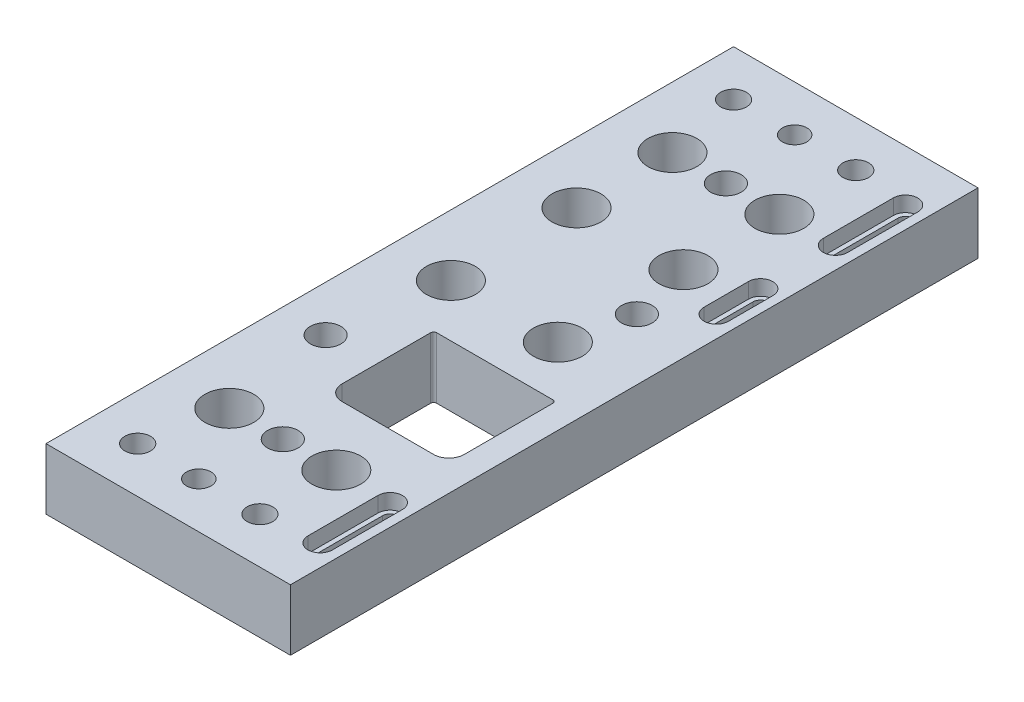
SolidWorks part; units mm, degrees
material "Plain Carbon Steel"
ref_plane "Front Plane" through (0, 0, 0) normal (0, 0, 1) x (1, 0, 0)
ref_plane "Top Plane" through (0, 0, 0) normal (0, 1, 0) x (1, 0, 0)
ref_plane "Right Plane" through (0, 0, 0) normal (1, 0, 0) x (0, 0, -1)
sketch "Sketch1" plane through (0, 0, 0) normal (0, 1, 0) x (1, 0, 0)
  line L1 (-40, -112.5) -> (40, -112.5)
  line L2 (-40, -112.5) -> (-40, 112.5)
  line L3 (-40, 112.5) -> (40, 112.5)
  line L4 (40, -112.5) -> (40, 112.5)
  line L5 (-40, -112.5) -> (40, 112.5) construction
  line L6 (-40, 112.5) -> (40, -112.5) construction
  point P0 (0, 0)
  dimension "D1" = 225
  dimension "D2" = 80
extrude "Boss-Extrude1" add sketch "Sketch1" against normal blind 20
sketch "Sketch2" plane through (0, 0, 0) normal (0, 1, 0) x (1, 0, 0)
  line L0 (23, -52.14) -> (26.5, -52.14) construction
  line L2 (31.5, -47.14) -> (31.5, -19.64) construction
  line L4 (31.5, -47.14) -> (31.5, -18.14)
  line L5 (-3.5, -52.14) -> (26.5, -52.14)
  line L6 (-8.5, -18.14) -> (-8.5, -47.14)
  line L7 (-7.5, -17.14) -> (30.5, -17.14)
  arc A2 (26.5, -52.14) -> (31.5, -47.14) centre (26.5, -47.14) ccw construction
  arc A5 (26.5, -52.14) -> (31.5, -47.14) centre (26.5, -47.14) ccw
  arc A6 (-8.5, -47.14) -> (-3.5, -52.14) centre (-3.5, -47.14) ccw
  arc A7 (30.5, -17.14) -> (31.5, -18.14) centre (30.5, -18.14) cw
  arc A8 (-7.5, -17.14) -> (-8.5, -18.14) centre (-7.5, -18.14) ccw
  dimension "D1" = 5
  dimension "D3" = 1
  dimension "D2" = 40
  dimension "D4" = 35
extrude "Cut-Extrude1" cut sketch "Sketch2" against normal up to next
sketch "Sketch3" plane through (0, 0, 0) normal (0, 1, 0) x (1, 0, 0)
  line L4 (35.5, -95.77) -> (35.5, -72.87)
  line L5 (30.5, -72.87) -> (30.5, -95.77)
  line L6 (35.5, -95.77) -> (35.5, -72.87)
  line L7 (30.5, -72.87) -> (30.5, -95.77)
  line L10 (35.5, 33.86) -> (35.5, 48.36)
  line L11 (30.5, 48.36) -> (30.5, 33.86)
  line L12 (35.5, 33.86) -> (35.5, 48.36)
  line L13 (30.5, 48.36) -> (30.5, 33.86)
  line L16 (35.5, 72.87) -> (35.5, 95.77)
  line L17 (30.5, 95.77) -> (30.5, 72.87)
  line L18 (35.5, 72.87) -> (35.5, 95.77)
  line L19 (30.5, 95.77) -> (30.5, 72.87)
  arc A4 (35.5, -72.87) -> (30.5, -72.87) centre (33, -72.87) ccw
  arc A5 (30.5, -95.77) -> (35.5, -95.77) centre (33, -95.77) ccw
  arc A6 (35.5, -72.87) -> (30.5, -72.87) centre (33, -72.87) ccw
  arc A7 (30.5, -95.77) -> (35.5, -95.77) centre (33, -95.77) ccw
  arc A10 (35.5, 48.36) -> (30.5, 48.36) centre (33, 48.36) ccw
  arc A11 (30.5, 33.86) -> (35.5, 33.86) centre (33, 33.86) ccw
  arc A12 (35.5, 48.36) -> (30.5, 48.36) centre (33, 48.36) ccw
  arc A13 (30.5, 33.86) -> (35.5, 33.86) centre (33, 33.86) ccw
  arc A16 (35.5, 95.77) -> (30.5, 95.77) centre (33, 95.77) ccw
  arc A17 (30.5, 72.87) -> (35.5, 72.87) centre (33, 72.87) ccw
  arc A18 (35.5, 95.77) -> (30.5, 95.77) centre (33, 95.77) ccw
  arc A19 (30.5, 72.87) -> (35.5, 72.87) centre (33, 72.87) ccw
  dimension "D1" = 0.05
  dimension "D2" = 0.05
  dimension "D3" = 0.05
extrude "Cut-Extrude2" cut sketch "Sketch3" against normal up to next
sketch "Sketch4" plane through (0, 0, 0) normal (0, 1, 0) x (1, 0, 0)
  line L4 (37, 72.87) -> (37, 95.77)
  line L5 (29, 95.77) -> (29, 72.87)
  line L6 (37, 72.87) -> (37, 95.77)
  line L7 (29, 95.77) -> (29, 72.87)
  line L10 (37, 33.86) -> (37, 48.36)
  line L11 (29, 48.36) -> (29, 33.86)
  line L12 (37, 33.86) -> (37, 48.36)
  line L13 (29, 48.36) -> (29, 33.86)
  line L16 (37, -95.77) -> (37, -72.87)
  line L17 (29, -72.87) -> (29, -95.77)
  line L18 (37, -95.77) -> (37, -72.87)
  line L19 (29, -72.87) -> (29, -95.77)
  arc A4 (37, 95.77) -> (29, 95.77) centre (33, 95.77) ccw
  arc A5 (29, 72.87) -> (37, 72.87) centre (33, 72.87) ccw
  arc A6 (37, 95.77) -> (29, 95.77) centre (33, 95.77) ccw
  arc A7 (29, 72.87) -> (37, 72.87) centre (33, 72.87) ccw
  arc A10 (37, 48.36) -> (29, 48.36) centre (33, 48.36) ccw
  arc A11 (29, 33.86) -> (37, 33.86) centre (33, 33.86) ccw
  arc A12 (37, 48.36) -> (29, 48.36) centre (33, 48.36) ccw
  arc A13 (29, 33.86) -> (37, 33.86) centre (33, 33.86) ccw
  arc A16 (37, -72.87) -> (29, -72.87) centre (33, -72.87) ccw
  arc A17 (29, -95.77) -> (37, -95.77) centre (33, -95.77) ccw
  arc A18 (37, -72.87) -> (29, -72.87) centre (33, -72.87) ccw
  arc A19 (29, -95.77) -> (37, -95.77) centre (33, -95.77) ccw
  dimension "D1" = 1.5
  dimension "D2" = 1.5
  dimension "D3" = 1.5
extrude "Cut-Extrude3" cut sketch "Sketch4" against normal blind 5
hole_wizard "CBORE for M8 Hex Head Bolt1" positions "Sketch9" profile "Sketch8" counterbore size "M8" standard "ISO" end condition through all
sketch "Sketch9" plane through (0, -20, 0) normal (0, -1, 0) x (-1, 0, 0)
  line L0 (40, -112.5) -> (-40, -112.5) construction
  line L1 (-40, -112.5) -> (-40, 112.5) construction
  line L2 (40, 112.5) -> (40, -112.5) construction
  line L3 (-40, 112.5) -> (40, 112.5) construction
  point P0 (25, 97.5)
  point P2 (-15, 97.5)
  point P4 (-15, -97.5)
  point P6 (25, -97.5)
  dimension "D1" = 15
  dimension "D2" = 25
  dimension "D3" = 15
  dimension "D4" = 15
sketch "Sketch8" plane through (-25, -20, -97.5) normal (1, 0, 0) x (0, 0, -1)
  line L0 (0, 0) -> (0, 20)
  line L1 (0, 20) -> (4.2, 20)
  line L3 (4.2, 20) -> (4.2, 5.3)
  line L4 (9.0055, 5.3) -> (4.2, 5.3)
  line L5 (9.0055, 5.3) -> (9.0055, 0.025)
  line L6 (9.0055, 0.025) -> (9.0305, 0)
  line L7 (9.0305, 0) -> (0, 0)
  line L8 (-9.0055, 0.025) -> (-9.0305, 0) construction
  line L11 (0, -6.35) -> (0, 107.95) construction
  dimension "Thru Hole Dia." = 8.4
  dimension "Thru Hole Depth" = 20
  dimension "C'Bore Dia." = 18.011
  dimension "C'Bore Depth" = 5.3
  dimension "Near C'Sink Dia." = 18.061
  dimension "Near C'Sink Angle" = 90
hole_wizard "Ø8.0mm Dowel Hole1" positions "Sketch12" profile "Sketch11" hole size "Ø8.0" standard "ISO" end condition through all
sketch "Sketch12" plane through (0, -20, 0) normal (0, -1, 0) x (-1, 0, 0)
  line L0 (25, 97.5) -> (-15, 97.5) construction
  line L2 (25, -97.5) -> (-15, -97.5) construction
  point P0 (5, -97.5)
  point P2 (5, 97.5)
sketch "Sketch11" plane through (-5, -20, 97.5) normal (1, 0, 0) x (0, 0, -1)
  line L0 (0, 0) -> (0, 20)
  line L1 (0, 20) -> (4, 20)
  line L2 (4, 20) -> (4, 0.025)
  line L3 (4, 0.025) -> (4.025, 0)
  line L5 (4.025, 0) -> (0, 0)
  line L6 (-4, 0.025) -> (-4.025, 0) construction
  line L11 (0, -6.35) -> (0, 107.95) construction
  dimension "Thru Hole Dia." = 8
  dimension "Thru Hole Depth" = 20
  dimension "Near C'Sink Dia." = 8.05
  dimension "Near C'Sink Angle" = 90
sketch "Sketch13" plane through (0, 0, 0) normal (0, 1, 0) x (1, 0, 0)
  circle A0 centre (15, 41.11) radius 8 construction
  circle A1 centre (15, 0) radius 8 construction
  circle A2 centre (15, -72.5) radius 8 construction
  circle A3 centre (-20, -72.5) radius 8 construction
  circle A4 centre (-20, 0) radius 8 construction
  circle A5 centre (-20, 41.11) radius 8 construction
  circle A6 centre (-20, 72.5) radius 8 construction
  circle A7 centre (15, 72.5) radius 8 construction
  circle A8 centre (15, 41.11) radius 8
  circle A9 centre (15, 0) radius 8
  circle A10 centre (15, -72.5) radius 8
  circle A11 centre (-20, -72.5) radius 8
  circle A12 centre (-20, 0) radius 8
  circle A13 centre (-20, 41.11) radius 8
  circle A14 centre (-20, 72.5) radius 8
  circle A15 centre (15, 72.5) radius 8
extrude "Cut-Extrude4" cut sketch "Sketch13" against normal up to next
sketch "Sketch15" plane through (0, 0, 0) normal (0, 1, 0) x (1, 0, 0)
  circle A0 centre (-2.5, -72.5) radius 5
  circle A1 centre (-25, -36) radius 5
  circle A2 centre (20, 20.8639) radius 5
  circle A3 centre (-2.5, 72.5) radius 5
  dimension "D1" = 10
extrude "Cut-Extrude5" cut sketch "Sketch15" against normal up to next
